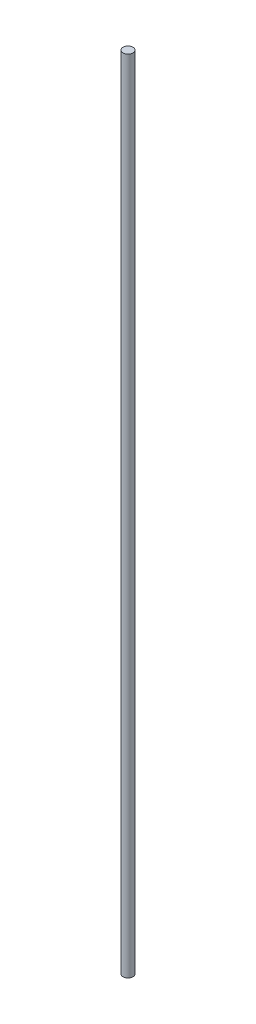
SolidWorks part; units mm, degrees
ref_plane "Front Plane" through (0, 0, 0) normal (0, 0, 1) x (1, 0, 0)
ref_plane "Top Plane" through (0, 0, 0) normal (0, 1, 0) x (1, 0, 0)
ref_plane "Right Plane" through (0, 0, 0) normal (1, 0, 0) x (0, 0, -1)
sketch "Sketch1" plane through (0, 0, 0) normal (0, 1, 0) x (1, 0, 0)
  circle A0 centre (0, 0) radius 5.08
extrude "Boss-Extrude1" add sketch "Sketch1" along normal blind 817.88
